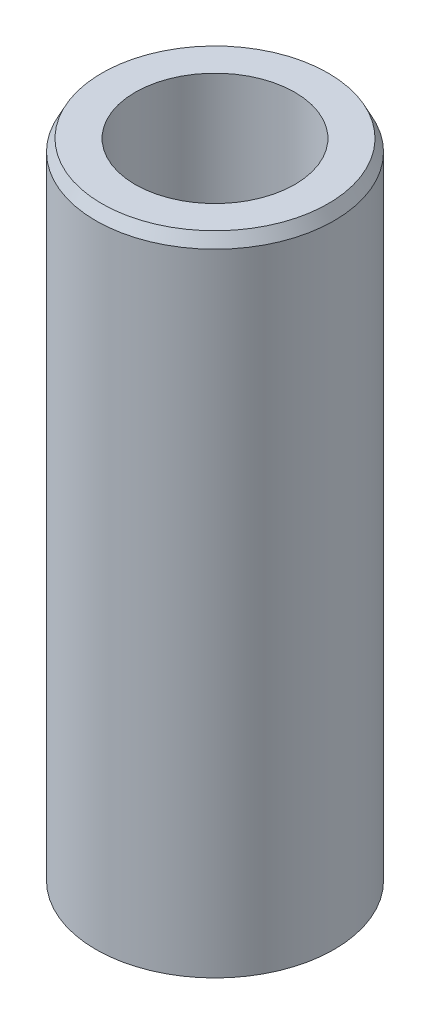
SolidWorks part; units mm, degrees
ref_plane "Front Plane" through (0, 0, 0) normal (0, 0, 1) x (1, 0, 0)
ref_plane "Top Plane" through (0, 0, 0) normal (0, 1, 0) x (1, 0, 0)
ref_plane "Right Plane" through (0, 0, 0) normal (1, 0, 0) x (0, 0, -1)
sketch "Sketch1" plane through (0, 0, 0) normal (0, 1, 0) x (1, 0, 0)
  circle A0 centre (0, 0) radius 57.5
  dimension "SHAFT_OD" = 115
extrude "Boss-Extrude1" add sketch "Sketch1" along normal blind 313.0818
sketch "Sketch2" plane through (0, 0, 0) normal (0, 1, 0) x (1, 0, 0)
  circle A0 centre (0, 0) radius 38.5424
  dimension "BORE_D" = 77.0849
extrude "Cut-Extrude1" cut sketch "Sketch2" along normal through all
chamfer "Chamfer1" distance 5.6703 angle 27.028 2 edges at (0, 313.0818, 57.5) (0, 0, 57.5) first distance on face at (0, 313.0818, 57.5) first distance on face at (0, 0, 38.5424)
